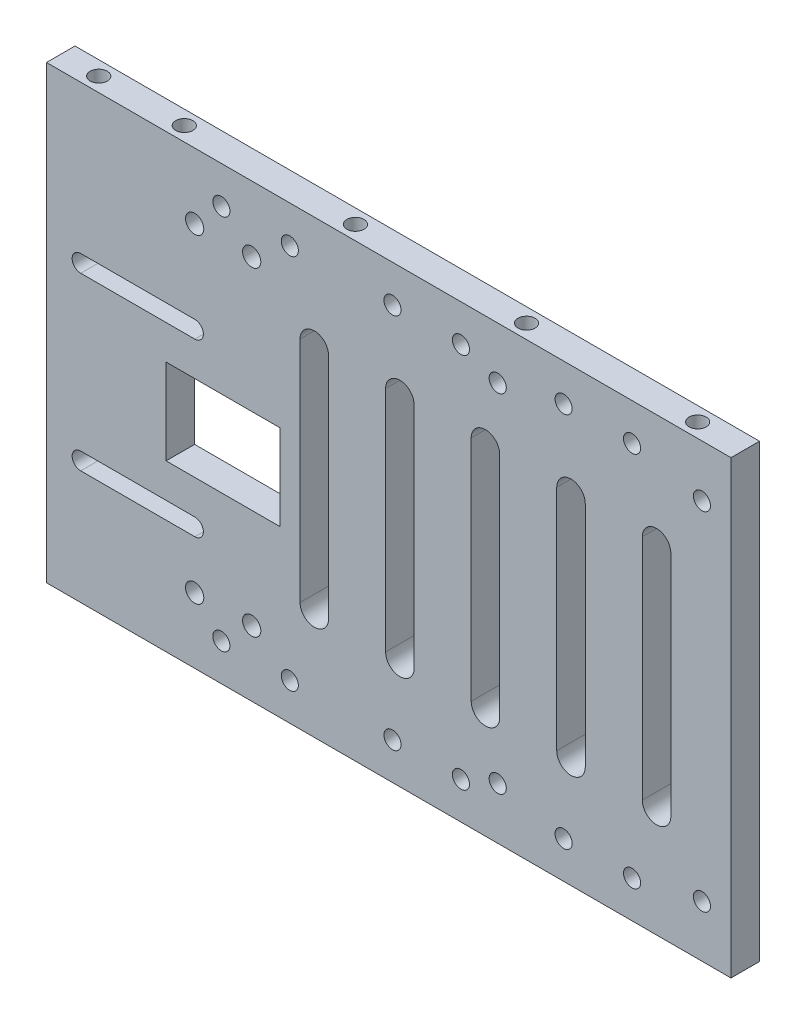
SolidWorks part; units mm, degrees
ref_plane "前视基准面" through (0, 0, 0) normal (0, 0, 1) x (1, 0, 0)
ref_plane "上视基准面" through (0, 0, 0) normal (0, 1, 0) x (1, 0, 0)
ref_plane "右视基准面" through (0, 0, 0) normal (1, 0, 0) x (0, 0, -1)
other "Configuration Table"
sketch "草图1" plane through (0, 0, 0) normal (0, 0, 1) x (1, 0, 0)
  line L1 (-60, -39.5) -> (60, -39.5)
  line L2 (-60, -39.5) -> (-60, 39.5)
  line L3 (-60, 39.5) -> (60, 39.5)
  line L4 (60, -39.5) -> (60, 39.5)
  line L5 (-60, -39.5) -> (60, 39.5) construction
  line L6 (-60, 39.5) -> (60, -39.5) construction
  point P0 (0, 0)
  dimension "D1" = 79
  dimension "D2" = 120
extrude "凸台-拉伸1" add sketch "草图1" along normal blind 5
sketch "草图2" plane through (0, 0, 0) normal (0, 0, -1) x (-1, 0, 0)
  circle A0 centre (-42.656, -33) radius 3.1
  circle A1 centre (-30.656, -33) radius 3.1
extrude "切除-拉伸1" cut sketch "草图2" against normal blind 2
sketch "草图3" plane through (0, 0, 2) normal (0, 0, -1) x (-1, 0, 0)
  circle A0 centre (-42.656, -33) radius 1.5
  circle A1 centre (-30.656, -33) radius 1.5
extrude "切除-拉伸2" cut sketch "草图3" against normal through all
pattern_linear "阵列(线性)1" count 3 spacing 30 along (-1, 0, 0) of "切除-拉伸1", "切除-拉伸2"
mirror "镜向2" about plane through (0, 0, 0) normal (0, 1, 0) of "阵列(线性)1"
sketch "草图4" plane through (0, 0, 0) normal (0, 0, -1) x (-1, 0, 0)
  line L0 (34, 12) -> (54, 12) construction
  line L1 (34, 15.1) -> (54, 15.1)
  line L2 (34, 8.9) -> (54, 8.9)
  line L3 (60, 39.5) -> (60, -39.5) construction
  line L4 (34.3421, -3) -> (54.815, -3) construction
  line L5 (34.3421, 17) -> (34.3421, -23) construction
  line L6 (54.815, 17) -> (54.815, -6) construction
  line L7 (34, -18) -> (54, -18) construction
  line L8 (34, -21.1) -> (54, -21.1)
  line L9 (34, -14.9) -> (54, -14.9)
  arc A4 (34, 15.1) -> (34, 8.9) centre (34, 12) ccw
  arc A5 (54, 8.9) -> (54, 15.1) centre (54, 12) ccw
  arc A6 (34, -21.1) -> (34, -14.9) centre (34, -18) cw
  arc A7 (54, -14.9) -> (54, -21.1) centre (54, -18) cw
  point P8 (44, 12)
  point P17 (44, -18)
  dimension "D1" = 20
  dimension "D2" = 6
extrude "切除-拉伸3" cut sketch "草图4" against normal blind 1.5
sketch "草图5" plane through (0, 0, 1.5) normal (0, 0, -1) x (-1, 0, 0)
  line L0 (54, 12) -> (34, 12) construction
  line L1 (54, 10.5) -> (34, 10.5)
  line L2 (54, 13.5) -> (34, 13.5)
  line L3 (60, 39.5) -> (60, -39.5) construction
  line L4 (34.3421, -3) -> (54.815, -3) construction
  line L5 (54.815, 17) -> (54.815, -6) construction
  line L6 (54, -18) -> (34, -18) construction
  line L7 (54, -16.5) -> (34, -16.5)
  line L8 (54, -19.5) -> (34, -19.5)
  arc A0 (54, 10.5) -> (54, 13.5) centre (54, 12) ccw
  arc A1 (34, 13.5) -> (34, 10.5) centre (34, 12) ccw
  arc A2 (54, -16.5) -> (54, -19.5) centre (54, -18) cw
  arc A3 (34, -19.5) -> (34, -16.5) centre (34, -18) cw
  point P4 (44, 12)
  point P18 (44, -18)
  dimension "D1" = 20
  dimension "D2" = 6
extrude "切除-拉伸4" cut sketch "草图5" against normal through all
sketch "草图7" plane through (0, -39.5, 0) normal (0, -1, 0) x (1, 0, 0)
  line L0 (46.656, 31) -> (46.656, 5) construction
  circle A0 centre (51.656, 2.5) radius 1.5
  circle A1 centre (21.656, 2.5) radius 1.5
  circle A2 centre (-8.344, 2.5) radius 1.5
  circle A3 centre (-38.344, 2.5) radius 1.5
  circle A4 centre (-53.344, 2.5) radius 1.5
  dimension "D1" = 5
  dimension "D2" = 15
extrude "切除-拉伸6" cut sketch "草图7" against normal blind 5
mirror "镜向3" about plane through (0, 0, 0) normal (0, 1, 0) of "切除-拉伸6"
sketch "草图9" plane through (0, 0, 0) normal (0, 0, -1) x (-1, 0, 0)
  line L0 (-46.9526, -20.2662) -> (-46.9526, 19.7338) construction
  line L1 (-49.4526, -20.2662) -> (-49.4526, 19.7338)
  line L2 (-44.4526, -20.2662) -> (-44.4526, 19.7338)
  line L3 (-31.9526, -20.2662) -> (-31.9526, 19.7338) construction
  line L4 (-34.4526, -20.2662) -> (-34.4526, 19.7338)
  line L5 (-29.4526, -20.2662) -> (-29.4526, 19.7338)
  line L6 (-16.9526, -20.2662) -> (-16.9526, 19.7338) construction
  line L7 (-19.4526, -20.2662) -> (-19.4526, 19.7338)
  line L8 (-14.4526, -20.2662) -> (-14.4526, 19.7338)
  line L9 (-1.9526, -20.2662) -> (-1.9526, 19.7338) construction
  line L10 (-4.4526, -20.2662) -> (-4.4526, 19.7338)
  line L11 (0.5474, -20.2662) -> (0.5474, 19.7338)
  line L12 (13.0474, -20.2662) -> (13.0474, 19.7338) construction
  line L13 (10.5474, -20.2662) -> (10.5474, 19.7338)
  line L14 (15.5474, -20.2662) -> (15.5474, 19.7338)
  circle A0 centre (24.0277, -28) radius 1.6 construction
  circle A1 centre (34.0277, -28) radius 1.6 construction
  circle A2 centre (24.0277, 28) radius 1.6 construction
  circle A3 centre (34.0277, 28) radius 1.6 construction
  circle A4 centre (24.0277, -28) radius 1.6
  circle A5 centre (34.0277, -28) radius 1.6
  circle A6 centre (24.0277, 28) radius 1.6
  circle A7 centre (34.0277, 28) radius 1.6
  arc A8 (-49.4526, -20.2662) -> (-44.4526, -20.2662) centre (-46.9526, -20.2662) ccw
  arc A9 (-44.4526, 19.7338) -> (-49.4526, 19.7338) centre (-46.9526, 19.7338) ccw
  arc A10 (-34.4526, -20.2662) -> (-29.4526, -20.2662) centre (-31.9526, -20.2662) ccw
  arc A11 (-29.4526, 19.7338) -> (-34.4526, 19.7338) centre (-31.9526, 19.7338) ccw
  circle A16 centre (-19.1038, 30.4) radius 1.5
  circle A17 centre (-54.9038, 30.4) radius 1.5
  circle A18 centre (-19.1038, -30.4) radius 1.5
  circle A19 centre (-54.9038, -30.4) radius 1.5
  arc A20 (-19.4526, -20.2662) -> (-14.4526, -20.2662) centre (-16.9526, -20.2662) ccw
  arc A21 (-14.4526, 19.7338) -> (-19.4526, 19.7338) centre (-16.9526, 19.7338) ccw
  arc A22 (-4.4526, -20.2662) -> (0.5474, -20.2662) centre (-1.9526, -20.2662) ccw
  arc A23 (0.5474, 19.7338) -> (-4.4526, 19.7338) centre (-1.9526, 19.7338) ccw
  arc A24 (10.5474, -20.2662) -> (15.5474, -20.2662) centre (13.0474, -20.2662) ccw
  arc A25 (15.5474, 19.7338) -> (10.5474, 19.7338) centre (13.0474, 19.7338) ccw
  point P17 (-46.9526, -0.2662)
  point P31 (-31.9526, -0.2662)
  point P38 (-16.9526, -0.2662)
  point P45 (-1.9526, -0.2662)
  point P52 (13.0474, -0.2662)
  dimension "D1" = 5
extrude "切除-拉伸7" cut sketch "草图9" against normal through all
sketch "草图11" plane through (0, 0, 5) normal (0, 0, 1) x (1, 0, 0)
  line L0 (-29.0277, 4.5) -> (-29.0277, -10.5)
  line L4 (-39.0277, -10.5) -> (-19.0277, -10.5)
  line L5 (-19.0277, -10.5) -> (-19.0277, 4.5)
  line L6 (-19.0277, 4.5) -> (-39.0277, 4.5)
  line L7 (-39.0277, 4.5) -> (-39.0277, -10.5)
  line L8 (-39.0277, -10.5) -> (-19.0277, -10.5)
  line L9 (-19.0277, -10.5) -> (-19.0277, 4.5)
  line L10 (-19.0277, 4.5) -> (-39.0277, 4.5)
  line L11 (-39.0277, 4.5) -> (-39.0277, -10.5)
  dimension "D1" = 0
extrude "切除-拉伸8" cut sketch "草图11" against normal through all contours L9 L10 L0 L8 | L10 L11 L8 L0 region at (-24.0277, -3, 5) region at (-34.0277, -3, 5)
